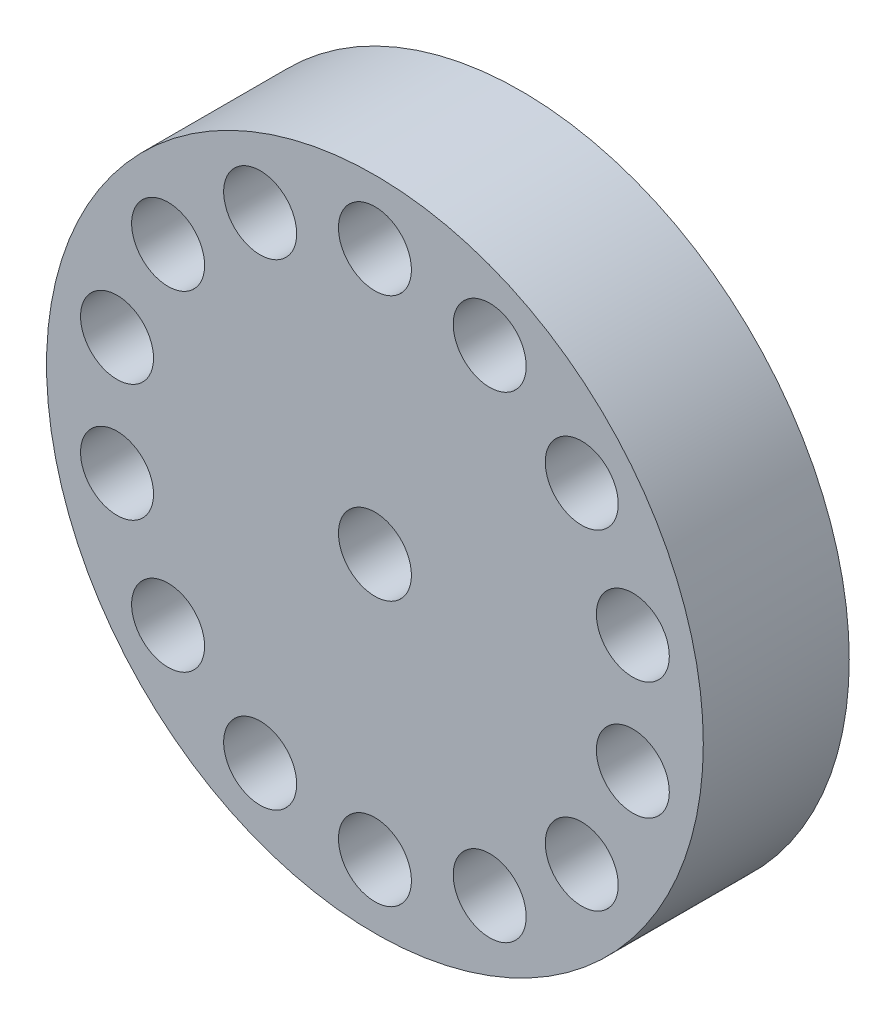
SolidWorks part; units mm, degrees
ref_plane "Płaszczyzna przednia" through (0, 0, 0) normal (0, 0, 1) x (1, 0, 0)
ref_plane "Płaszczyzna górna" through (0, 0, 0) normal (0, 1, 0) x (1, 0, 0)
ref_plane "Płaszczyzna prawa" through (0, 0, 0) normal (1, 0, 0) x (0, 0, -1)
sketch "Szkic1" plane through (0, 0, 0) normal (0, 0, 1) x (1, 0, 0)
  circle A0 centre (0, 0) radius 4.5
  circle A1 centre (0, 0) radius 0.5
extrude "Dodanie-wyciągnięcie1" add sketch "Szkic1" along normal blind 2
sketch "Szkic2" plane through (0, 0, 2) normal (0, 0, 1) x (1, 0, 0)
  circle A0 centre (0, 3.625) radius 0.5
  circle A1 centre (1.5728, 3.266) radius 0.5
  circle A2 centre (2.8341, 2.2602) radius 0.5
  circle A3 centre (3.5341, 0.8066) radius 0.5
  circle A4 centre (3.5341, -0.8066) radius 0.5
  circle A5 centre (2.8341, -2.2602) radius 0.5
  circle A6 centre (1.5728, -3.266) radius 0.5
  circle A7 centre (0, -3.625) radius 0.5
  circle A8 centre (-1.5728, -3.266) radius 0.5
  circle A9 centre (-2.8341, -2.2602) radius 0.5
  circle A10 centre (-3.5341, -0.8066) radius 0.5
  circle A11 centre (-3.5341, 0.8066) radius 0.5
  circle A12 centre (-2.8341, 2.2602) radius 0.5
  circle A13 centre (-1.5728, 3.266) radius 0.5
  point P31 (0, 0)
  dimension "D1" = 1
  dimension "D2" = 3.625
  dimension "D3" = 14
extrude "Wytnij-wyciągnięcie1" cut sketch "Szkic2" against normal blind 1
